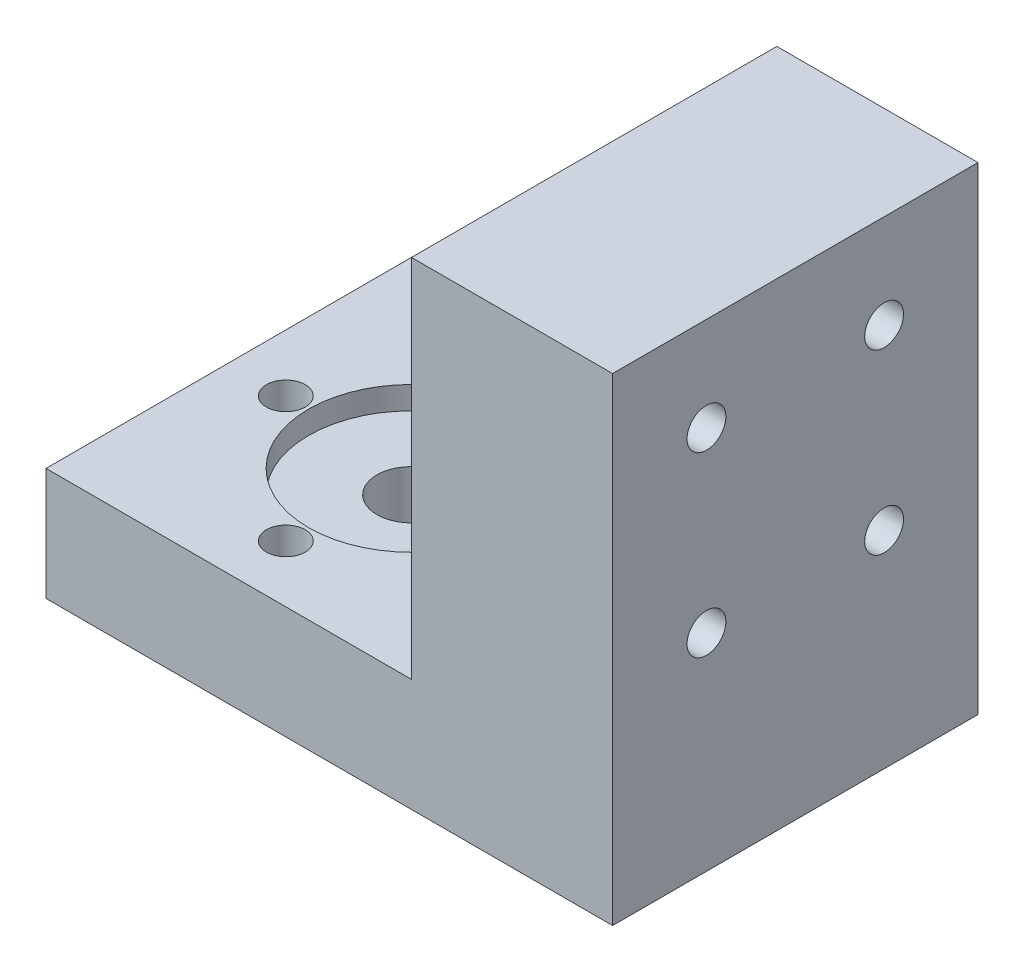
SolidWorks part; units mm, degrees
ref_plane "Front Plane" through (0, 0, 0) normal (0, 0, 1) x (1, 0, 0)
ref_plane "Top Plane" through (0, 0, 0) normal (0, 1, 0) x (1, 0, 0)
ref_plane "Right Plane" through (0, 0, 0) normal (1, 0, 0) x (0, 0, -1)
sketch "Sketch1" plane through (0, 0, 0) normal (0, 1, 0) x (1, 0, 0)
  line L1 (-16, -16) -> (16, -16)
  line L2 (-16, -16) -> (-16, 16)
  line L3 (-16, 16) -> (16, 16)
  line L4 (16, -16) -> (16, 16)
  line L5 (-16, -16) -> (16, 16) construction
  line L6 (-16, 16) -> (16, -16) construction
  circle A0 centre (0, 0) radius 3.02
  circle A1 centre (0, 0) radius 9
  circle A3 centre (0, 0) radius 11
  circle A4 centre (0, 11) radius 1.7
  circle A6 centre (-11, 0) radius 1.7
  circle A8 centre (0, -11) radius 1.7
  circle A9 centre (11, 0) radius 1.7
  dimension "D1" = 6.04
  dimension "D2" = 18
  dimension "D6" = 22
  dimension "D3" = 3.4
  dimension "D4" = 32
  dimension "D5" = 32
extrude "Boss-Extrude1" add sketch "Sketch1" against normal blind 9.8648 contours L1 L4 L3 L2 | A1 | A1 A0 region at (-15.5475, 0, 0) region at (-8.7454, 0, 0) region at (9.2693, 0, 0)
extrude "Cut-Extrude2" cut sketch "Sketch1<5>" against normal blind 2 contours A1
sketch "Sketch1<5>" plane through (0, 0, 0) normal (0, 1, 0) x (1, 0, 0) same geometry as "Sketch1"
sketch "Sketch7" plane through (16, 0, 0) normal (1, 0, 0) x (0, 0, -1)
  line L2 (-16, 0) -> (16, 0)
  line L3 (-16, 0) -> (-16, -9.8648)
  line L4 (-16, -9.8648) -> (16, -9.8648)
  line L5 (16, 0) -> (16, -9.8648)
extrude "Boss-Extrude3" add sketch "Sketch7" along normal blind 17.6139
sketch "Sketch10" plane through (0, 0, 0) normal (0, 1, 0) x (1, 0, 0)
  line L1 (16, 16) -> (33.6139, 16)
  line L2 (16, 16) -> (16, -16)
  line L3 (16, -16) -> (33.6139, -16)
  line L4 (33.6139, 16) -> (33.6139, -16)
extrude "Boss-Extrude5" add sketch "Sketch10" along normal blind 32
sketch "Sketch11" plane through (16, 0, 0) normal (-1, 0, 0) x (0, 0, 1)
  line L0 (0, 16) -> (-7.7782, 23.7782) construction
  line L1 (-16, 32) -> (16, 32)
  line L2 (-16, 32) -> (-16, 0)
  line L3 (-16, 0) -> (16, 0)
  line L4 (16, 32) -> (16, 0)
  line L5 (-11, 16) -> (11, 16) construction
  line L6 (0, 27) -> (0, 5) construction
  circle A0 centre (0, 16) radius 11
  circle A1 centre (-7.7782, 23.7782) radius 1.7
  circle A2 centre (7.7782, 23.7782) radius 1.7
  circle A3 centre (7.7782, 8.2218) radius 1.7
  circle A4 centre (-7.7782, 8.2218) radius 1.7
  point P23 (0, 16)
  dimension "D3" = 3.4
  dimension "D1" = 22
  dimension "D2" = 4
extrude "Cut-Extrude3" cut sketch "Sketch11" against normal through all contours A1 | A4 | A3 | A2
equation "\"P\"= 300"
equation "\"delt\"= .3mm"
equation "\"sf\"= 3"
equation "\"E\"= 3600"
equation "\"stress_y\"= 60"
equation "\"b\" = 32mm"
equation "\"L_1\"= \"b\""
equation "\"M_1\"= \"P\" * 18"
equation "\"stress\"= \"stress_y\" / \"sf\""
equation "\"h1_1\" = sqr ( ( \"M_1\" * 6 ) / ( \"b\" * \"stress\" ) )"
equation "\"h1_2\"= ( ( \"M_1\" * ( \"L_1\" ^ 2 ) * 6 ) / ( \"b\" * \"E\" * \"delt\" ) ) ^ ( 1 / 3 )"
equation "\"L_2\"= \"h1_2\" + \"L_1\""
equation "\"M_2\"= \"P\" * ( 18 + \"L_2\" )"
equation "\"h2_1\"= sqr ( ( \"M_2\" * 6 ) / ( \"b\" * \"stress\" ) )"
equation "\"h2_2\" = ( ( \"M_2\" * ( \"L_2\" ^ 2 ) * 6 ) / ( \"b\" * \"E\" * \"delt\" ) ) ^ ( 1 / 3 )"
equation "\"h1\"= \"h1_2\""
equation "\"h2\"= \"h2_2\""
equation "\"d1\"= 6.04mm"
equation "\"d_2\"= 18mm"
equation "\"d_3\"= 22mm"
equation "\"D1@Sketch1\"=\"d1\""
equation "\"D2@Sketch1\"=\"d_2\""
equation "\"D5@Sketch1\"=\"L_1\""
equation "\"D4@Sketch1\"=\"b\""
equation "\"D1@Boss-Extrude1\"=\"h1\""
equation "\"D6@Sketch1\"=\"d_3\""
equation "\"D1@Boss-Extrude3\"=\"h2\""
equation "\"D1@Boss-Extrude5\"=\"L_1\""
equation "\"D1@Sketch11\"=\"d_3\""
equation "\"m3\"= 3.4mm"
equation "\"D3@Sketch11\"=\"m3\""
equation "\"D3@Sketch1\"=\"m3\""
